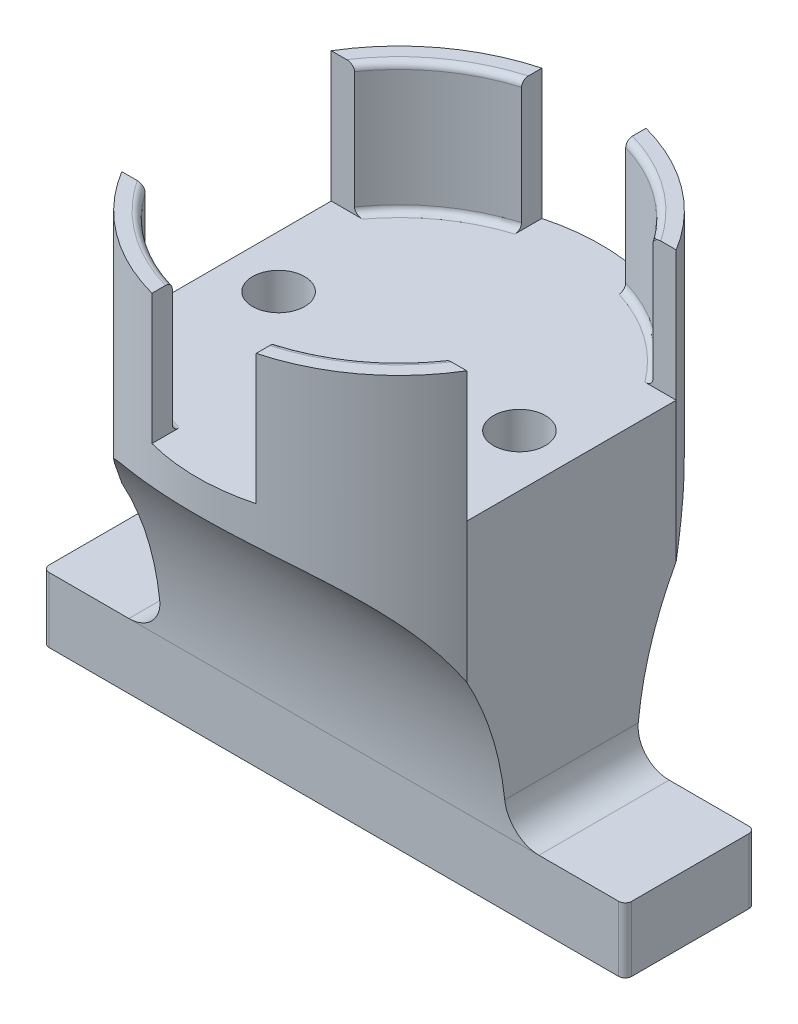
SolidWorks part; units mm, degrees
material "PBT Общее назначение"
ref_plane "Спереди" through (0, 0, 0) normal (0, 0, 1) x (1, 0, 0)
ref_plane "Сверху" through (0, 0, 0) normal (0, 1, 0) x (1, 0, 0)
ref_plane "Справа" through (0, 0, 0) normal (1, 0, 0) x (0, 0, -1)
sketch "Эскиз1" plane through (0, 0, 0) normal (0, 1, 0) x (1, 0, 0)
  circle A0 centre (0, 0) radius 28
  circle A1 centre (0, 0) radius 31
  dimension "D1" = 56
  dimension "D2" = 62
extrude "Бобышка-Вытянуть1" add sketch "Эскиз1" along normal blind 20
sketch "Эскиз2" plane through (0, 0, 0) normal (0, -1, 0) x (1, 0, 0)
  circle A0 centre (0, 0) radius 31 construction
  circle A1 centre (0, 0) radius 31
extrude "Бобышка-Вытянуть2" add sketch "Эскиз2" along normal blind 5
sketch "Эскиз3" plane through (0, -5, 0) normal (0, -1, 0) x (1, 0, 0)
  line L0 (-31, 0) -> (31, 0) construction
  line L1 (-31, 10) -> (31, 10)
  line L2 (-31, 10) -> (-31, -10) construction
  line L3 (31, 10) -> (31, -10) construction
  line L4 (-31, -10) -> (31, -10)
  line L5 (-31, 0) -> (31, 0) construction
  line L6 (0, 10) -> (0, -31) construction
  line L7 (0, 10) -> (0, -10) construction
  circle A0 centre (0, 0) radius 31 construction
  arc A1 (29.3428, -10) -> (29.3428, 10) centre (0, 0) ccw
  arc A2 (-29.3428, 10) -> (-29.3428, -10) centre (0, 0) ccw
  circle M9 centre (0, 0) radius 31
  dimension "D1" = 20
extrude "Бобышка-Вытянуть3" add sketch "Эскиз3" along normal blind 40 contours L4 L1 M9
sketch "Эскиз6" plane through (0, -45, 0) normal (0, -1, 0) x (1, 0, 0)
  line L0 (44.75, -10) -> (-44.75, -10)
  line L1 (44.75, -10) -> (44.75, 10)
  line L2 (-44.75, -10) -> (-44.75, 10)
  line L3 (44.75, 10) -> (-44.75, 10)
  line L4 (0, -10) -> (0, 10) construction
  line L5 (-29.3428, -10) -> (29.3428, -10) construction
  line L6 (-29.3428, 10) -> (29.3428, 10) construction
  line L7 (0, -10) -> (0, 10) construction
  dimension "D1" = 89.5
extrude "Бобышка-Вытянуть4" add sketch "Эскиз6" along normal blind 10
ref_plane "Плоскость1" through (-29.3428, 0, 0) normal (1, 0, 0) x (0, 0, -1)
ref_plane "Плоскость2" through (29.3428, 0, 0) normal (-1, 0, 0) x (0, 0, 1)
sketch "Эскиз7" plane through (-29.3428, 0, 0) normal (1, 0, 0) x (0, 0, -1)
  line L0 (10, -45) -> (10, -5) construction
  line L1 (10, -45) -> (10, -5)
  line L2 (10, -5) -> (31, -5) construction
  line L3 (10, -5) -> (31, -5)
  arc A0 (31, -5) -> (10, -45) centre (58.5952, -45) ccw
extrude "Бобышка-Вытянуть5" add sketch "Эскиз7" along normal up to surface (58.6856 mm away) up to plane "Плоскость2"
sketch "Эскиз8" plane through (0, -5, 0) normal (0, 1, 0) x (1, 0, 0)
  line L2 (29.3428, 31) -> (0, 31)
  line L3 (29.3428, 10) -> (29.3428, 31)
  line L4 (29.3428, 31) -> (0, 31)
  line L5 (29.3428, 10) -> (29.3428, 31)
  line L6 (-29.3428, 31) -> (-29.3428, 10)
  line L7 (0, 31) -> (-29.3428, 31)
  line L8 (-29.3428, 31) -> (-29.3428, 10)
  line L9 (0, 31) -> (-29.3428, 31)
  arc A1 (29.3428, 10) -> (0, 31) centre (0, 0) ccw
  arc A2 (29.3428, 10) -> (0, 31) centre (0, 0) ccw
  arc A3 (0, 31) -> (-29.3428, 10) centre (0, 0) ccw
  arc A4 (0, 31) -> (-29.3428, 10) centre (0, 0) ccw
  dimension "D1" = 0
  dimension "D2" = 0
extrude "Вырез-Вытянуть3" cut sketch "Эскиз8" against normal through all contours A4 L9 L8
sketch "Эскиз9" plane through (0, -55, 0) normal (0, -1, 0) x (1, 0, 0)
  line L0 (-44.75, 0) -> (44.75, 0) construction
  line L1 (-44.75, 10) -> (-44.75, -10) construction
  line L2 (44.75, -10) -> (44.75, 10) construction
  line L3 (0, 10) -> (0, -10) construction
  line L4 (44.75, 10) -> (-44.75, 10) construction
  line L5 (-44.75, -10) -> (44.75, -10) construction
ref_plane "СиммZ" through (0, 0, 0) normal (0, 0, -1) x (1, 0, 0)
mirror "Зеркальное отражение1" about plane through (0, 0, 0) normal (0, 0, -1) of "Вырез-Вытянуть3", "Бобышка-Вытянуть5"
ref_plane "СиммX" through (0, 0, 0) normal (-1, 0, 0) x (0, 0, -1)
fillet "Скругление3" radius 1 2 edges at (0, 20, 28) (0, 0, 28)
sketch "Эскиз11" plane through (0, 20, 0) normal (0, 1, 0) x (1, 0, 0)
  line L0 (8, -31) -> (-8, -31)
  line L1 (8, -31) -> (8, 31)
  line L2 (-8, -31) -> (-8, 31)
  line L3 (8, 31) -> (-8, 31)
  line L4 (0, -31) -> (0, 31) construction
  line L5 (0, -31) -> (0, 31) construction
  circle A0 centre (0, 0) radius 31 construction
  dimension "D1" = 16
extrude "Вырез-Вытянуть5" cut sketch "Эскиз11" against normal up to surface (20 mm away) up to face at (0, 0, -27)
fillet "Скругление4" radius 1 4 edges at (-44.75, -50, 10) (-44.75, -50, -10) (44.75, -50, -10) (44.75, -50, 10)
sketch "Эскиз12" plane through (0, 20, 0) normal (0, 1, 0) x (1, 0, 0)
  line L0 (-44.75, -9) -> (-44.75, 9) construction
  line L1 (44.75, 9) -> (44.75, -9) construction
  line L2 (-44.75, -9) -> (-44.75, 9) construction
  line L3 (44.75, 9) -> (44.75, -9) construction
  line L4 (44.75, 0) -> (-44.75, 0) construction
  line L5 (0, 0) -> (0, -41.9153) construction
  line L6 (26.5, -31) -> (26.5, 31) construction
  line L7 (26.5, -31) -> (-26.5, -31) construction
  line L8 (26.5, 31) -> (-26.5, 31) construction
  line L9 (-26.5, -31) -> (-26.5, 31) construction
  line L10 (0, -31) -> (0, 31) construction
  line L13 (26.5, -16.0857) -> (26.5, 16.0857)
  line L14 (-26.5, -16.0857) -> (-26.5, 16.0857)
  arc A0 (-8, -29.95) -> (8, -29.95) centre (0, 0) ccw construction
  arc A1 (-8, -29.95) -> (8, -29.95) centre (0, 0) ccw construction
  arc A2 (8, 29.95) -> (-8, 29.95) centre (0, 0) ccw construction
  arc A3 (8, 29.95) -> (-8, 29.95) centre (0, 0) ccw construction
  arc A4 (-8, 29.95) -> (-8, -29.95) centre (0, 0) ccw construction
  arc A5 (-26.5, 16.0857) -> (-26.5, -16.0857) centre (0, 0) ccw
  arc A6 (8, -29.95) -> (8, 29.95) centre (0, 0) ccw construction
  arc A7 (26.5, -16.0857) -> (26.5, 16.0857) centre (0, 0) ccw
  dimension "D1" = 53
extrude "Вырез-Вытянуть6" cut sketch "Эскиз12" against normal up to surface (65 mm away) up to face at (39.35, -45, -1.6667)
fillet "Скругление5" radius 5 2 edges at (26.5, -45, 0) (-26.5, -45, 0)
sketch "Эскиз13" plane through (0, 0, 0) normal (0, 1, 0) x (1, 0, 0)
  line L0 (0, 0) -> (-26.5, 0) construction
  line L1 (-26.5, 5.172) -> (-26.5, -5.172) construction
  line L2 (0, 0) -> (26.5, 0) construction
  line L3 (26.5, -5.172) -> (26.5, 5.172) construction
  line L4 (0, 0) -> (0, -31) construction
  circle A0 centre (18.5, 0) radius 4
  arc A1 (-8, -29.95) -> (8, -29.95) centre (0, 0) ccw construction
  circle A2 centre (-18.5, 0) radius 4
  dimension "D1" = 8
  dimension "D2" = 8
extrude "Вырез-Вытянуть7" cut sketch "Эскиз13" against normal up to surface (45 mm away) up to face at (40.069, -45, 0)
sketch "Эскиз14" plane through (0, -45, 0) normal (0, 1, 0) x (1, 0, 0)
  circle A0 centre (18.5, 0) radius 4 construction
  circle A1 centre (18.5, 0) radius 4 construction
  circle A2 centre (-18.5, 0) radius 4 construction
  circle A3 centre (-18.5, 0) radius 4 construction
  circle A4 centre (18.5, 0) radius 2.1
  circle A5 centre (-18.5, 0) radius 2.1
  dimension "D1" = 4.2
  dimension "D2" = 4.2
extrude "Вырез-Вытянуть8" cut sketch "Эскиз14" against normal through all
sketch "Эскиз15" plane through (0, 20, 0) normal (0, 1, 0) x (1, 0, 0)
  line L0 (26.5, -16.0857) -> (-26.5, -16.0857)
  line L1 (26.5, -16.0857) -> (26.5, 16.0857)
  line L2 (-26.5, -16.0857) -> (-26.5, 16.0857)
  line L3 (26.5, 16.0857) -> (-26.5, 16.0857)
extrude "Вырез-Вытянуть9" cut sketch "Эскиз15" against normal up to surface (20 mm away) up to face at (-18.5, 0, -4)
